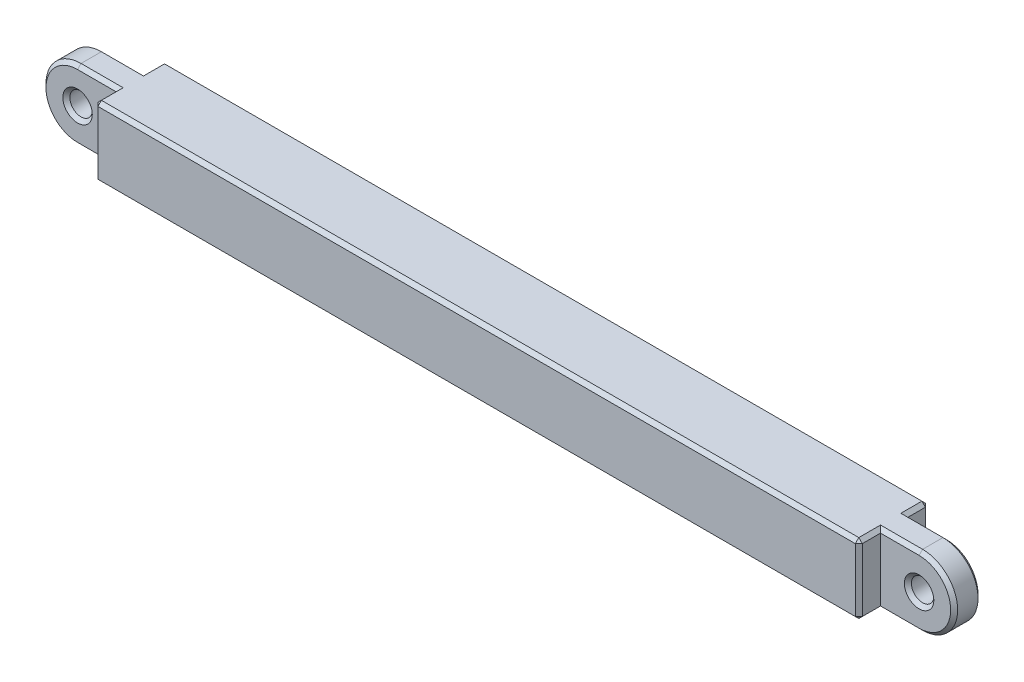
SolidWorks part; units mm, degrees
ref_plane "Front" through (0, 0, 0) normal (0, 0, 1) x (1, 0, 0)
ref_plane "Top" through (0, 0, 0) normal (0, 1, 0) x (1, 0, 0)
ref_plane "Right" through (0, 0, 0) normal (1, 0, 0) x (0, 0, -1)
sketch "Sketch1" plane through (0, 0, 0) normal (0, 0, 1) x (1, 0, 0)
  line L0 (0, 5) -> (120, 5)
  line L1 (0, -5) -> (120, -5)
  circle A0 centre (0, 0) radius 5 construction
  circle A1 centre (120, 0) radius 5 construction
  arc A2 (120, -5) -> (120, 5) centre (120, 0) ccw
  arc A3 (0, 5) -> (0, -5) centre (0, 0) ccw
  circle A4 centre (0, 0) radius 1.6
  circle A5 centre (120, 0) radius 1.6
extrude "Boss-Extrude1" add sketch "Sketch1" along normal blind 1.95 and the other way blind 1.95
sketch "Sketch2" plane through (0, 0, 1.95) normal (0, 0, 1) x (1, 0, 0)
  line L0 (5.5, 5) -> (114.5, 5)
  line L1 (120, 5) -> (0, 5) construction
  line L2 (114.5, 5) -> (114.5, -5)
  line L3 (0, -5) -> (120, -5) construction
  line L4 (114.5, -5) -> (5.5, -5)
  line L5 (5.5, -5) -> (5.5, 5)
  circle A0 centre (0, 0) radius 5 construction
  circle A1 centre (120, 0) radius 5 construction
  dimension "D1" = 5.5
  dimension "D2" = 5.5
extrude "Boss-Extrude2" add sketch "Sketch2" along normal blind 3.1 and the other way blind 6.9
chamfer "Chamfer1" distance 0.5 angle 45 32 edges at (125, 0, -1.95) (-5, 0, -1.95) (2.75, 5, -1.95) (5.5, 5, -3.45) (117.25, 5, -1.95) (114.5, 5, -3.45) (114.5, 0, -4.95) (60, 5, -4.95) (5.5, 0, -4.95) (117.25, -5, -1.95) (114.5, -5, -3.45) (60, -5, -4.95) (5.5, -5, -3.45) (2.75, -5, -1.95) (-5, 0, 1.95) (125, 0, 1.95) (117.25, 5, 1.95) (114.5, 5, 3.5) (2.75, 5, 1.95) (5.5, 5, 3.5) (2.75, -5, 1.95) (5.5, -5, 3.5) (117.25, -5, 1.95) (114.5, -5, 3.5) (60, 5, 5.05) (114.5, 0, 5.05) (60, -5, 5.05) (5.5, 0, 5.05) (121.6, 0, 1.95) (121.6, 0, -1.95) (1.6, 0, 1.95) (1.6, 0, -1.95)
